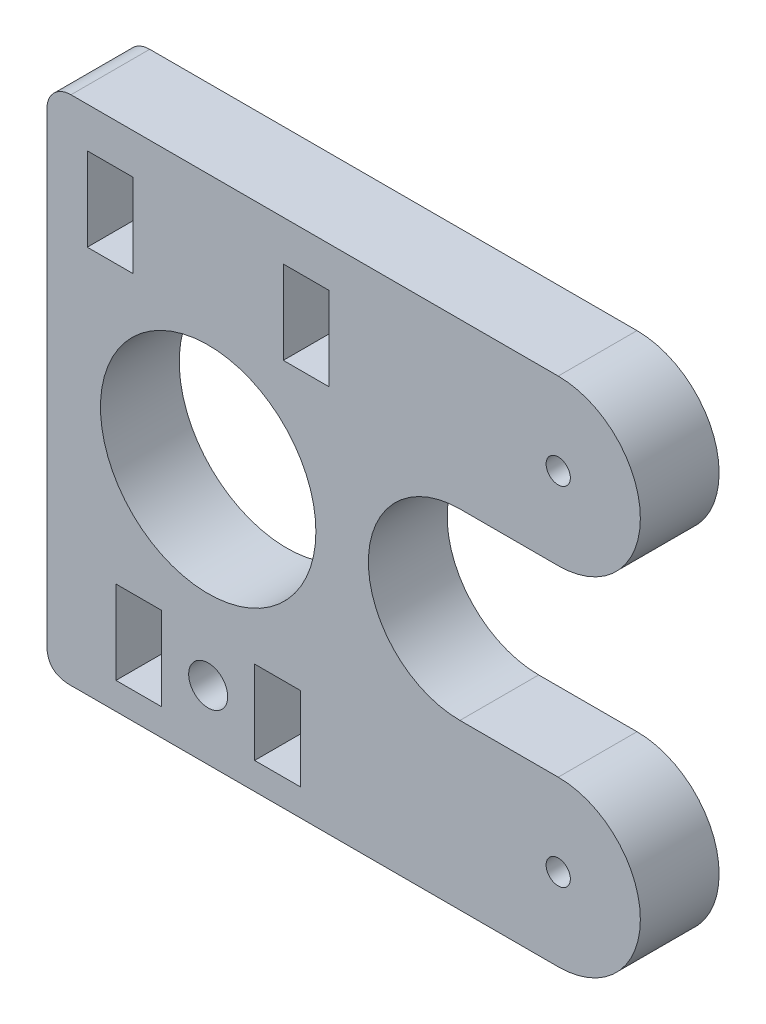
SolidWorks part; units mm, degrees
material "Acrylic (Medium-high impact)"
ref_plane "Front Plane" through (0, 0, 0) normal (0, 0, 1) x (1, 0, 0)
ref_plane "Top Plane" through (0, 0, 0) normal (0, 1, 0) x (1, 0, 0)
ref_plane "Right Plane" through (0, 0, 0) normal (1, 0, 0) x (0, 0, -1)
sketch "Sketch1" plane through (0, 0, 0) normal (0, 0, 1) x (1, 0, 0)
  line L0 (669.2168, 349.7655) -> (648.5357, 349.7655)
  line L1 (646.7465, 347.9762) -> (646.7465, 313.4546)
  line L2 (648.7733, 311.7655) -> (669.2168, 311.7655)
  line L3 (653.1465, 340.5655) -> (653.1465, 346.7655)
  line L4 (653.1465, 346.7655) -> (649.7465, 346.7655)
  line L5 (649.7465, 346.7655) -> (649.7465, 340.5655)
  line L6 (649.7465, 340.5655) -> (653.1465, 340.5655)
  line L7 (651.8765, 313.7655) -> (655.2765, 313.7655)
  line L8 (655.2765, 313.7655) -> (655.2765, 319.9655)
  line L9 (655.2765, 319.9655) -> (651.8765, 319.9655)
  line L10 (651.8765, 319.9655) -> (651.8765, 313.7655)
  line L11 (667.7065, 340.5655) -> (667.7065, 346.7655)
  line L12 (667.7065, 346.7655) -> (664.3065, 346.7655)
  line L13 (664.3065, 346.7655) -> (664.3065, 340.5655)
  line L14 (664.3065, 340.5655) -> (667.7065, 340.5655)
  line L15 (662.1765, 319.9655) -> (662.1765, 313.7655)
  line L16 (662.1765, 313.7655) -> (665.5765, 313.7655)
  line L17 (665.5765, 313.7655) -> (665.5765, 319.9655)
  line L18 (665.5765, 319.9655) -> (662.1765, 319.9655)
  line L19 (-318.4867, 330.7655) -> (49681.5133, 330.7655) construction
  line L20 (669.2168, -652.8598) -> (669.2168, 49347.1402) construction
  line L21 (653.1465, 340.5655) -> (664.3065, 340.5655) construction
  line L22 (657.2765, 316.8655) -> (655.2765, 316.8655) construction
  line L23 (660.1765, 316.8655) -> (662.1765, 316.8655) construction
  line L24 (658.7265, -666.0306) -> (658.7265, 49333.9694) construction
  line L25 (669.2168, 311.7655) -> (684.7265, 311.7655)
  line L26 (669.2168, 349.7655) -> (684.7265, 349.7655)
  line L27 (684.7265, 317.8655) -> (684.7265, 330.7655) construction
  line L28 (684.7265, 330.7655) -> (684.7265, 343.6655) construction
  line L29 (684.7265, -670.5722) -> (684.7265, 49329.4278) construction
  line L30 (662.1765, 330.7655) -> (662.1765, 349.7655) construction
  line L31 (662.1765, 330.7655) -> (662.1765, 311.7655) construction
  line L32 (684.7265, 337.5655) -> (677.4255, 337.5655)
  line L33 (684.7265, 323.9655) -> (677.4255, 323.9655)
  circle A0 centre (684.7265, 343.6655) radius 0.8999
  circle A1 centre (684.7265, 317.8655) radius 0.8999
  arc A2 (684.7265, 311.7655) -> (684.7265, 323.9655) centre (684.7265, 317.8655) ccw
  circle A3 centre (658.7265, 316.8655) radius 1.45
  arc A4 (646.7465, 347.9762) -> (648.5357, 349.7655) centre (648.5357, 347.9762) cw
  arc A5 (684.7265, 349.7655) -> (684.7265, 337.5655) centre (684.7265, 343.6655) cw
  arc A6 (677.4255, 337.5655) -> (677.4255, 323.9655) centre (677.4255, 330.7655) ccw
  circle A8 centre (658.7265, 330.7655) radius 8
  spline S7 degree 2 poles (646.7465, 313.4546) (646.7465, 311.6465) (648.7733, 311.7655) knots 0 0 0 1 1 1
  point P27 (658.7265, 340.5655)
  dimension "D5" = 2.9
  dimension "D12" = 26
  dimension "D1" = 2
  dimension "D2" = 6.2
  dimension "D3" = 3.4
  dimension "D4" = 3.4
  dimension "D6" = 11.16
  dimension "D7" = 3
  dimension "D8" = 3
  dimension "D9" = 2
  dimension "D10" = 33
  dimension "D11" = 12.9
extrude "Boss-Extrude2" add sketch "Sketch1" along normal blind 5.85
